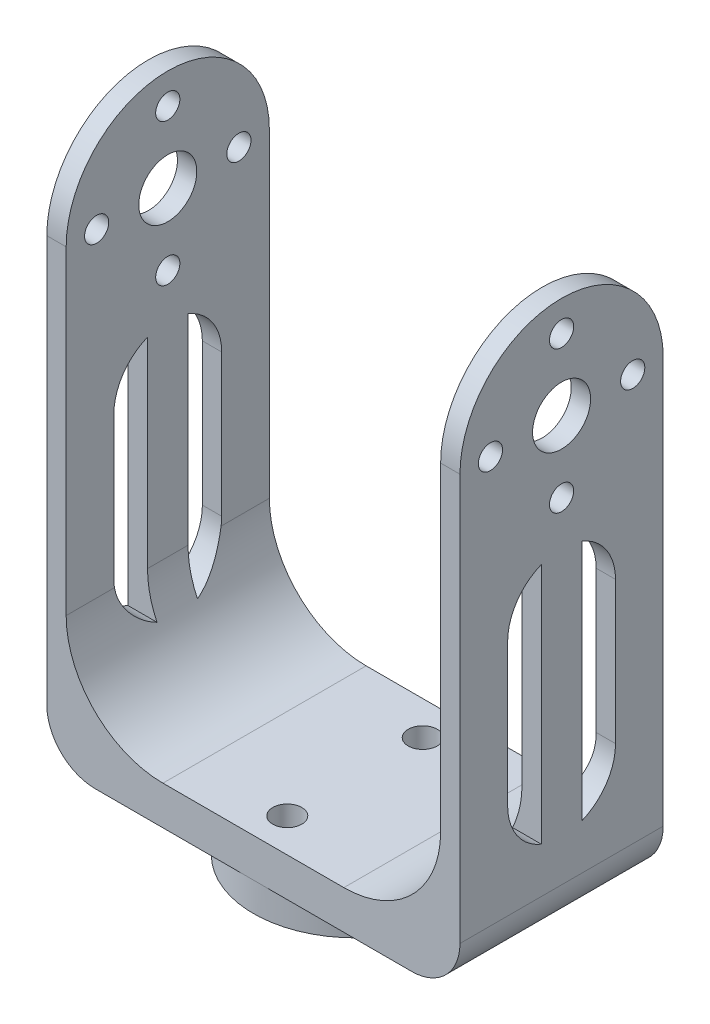
SolidWorks part; units mm, degrees
ref_plane "前视基准面" through (0, 0, 0) normal (0, 0, 1) x (1, 0, 0)
ref_plane "上视基准面" through (0, 0, 0) normal (0, 1, 0) x (1, 0, 0)
ref_plane "右视基准面" through (0, 0, 0) normal (1, 0, 0) x (0, 0, -1)
other "Configuration Table"
sketch "草图1" plane through (0, 0, 0) normal (0, 1, 0) x (1, 0, 0)
  line L0 (0, 10.5) -> (0, -10.5) construction
  line L1 (-21.35, 10.5) -> (21.35, 10.5)
  line L2 (-21.35, 10.5) -> (-21.35, -10.5)
  line L3 (-21.35, -10.5) -> (21.35, -10.5)
  line L4 (21.35, 10.5) -> (21.35, -10.5)
  line L5 (-21.35, 10.5) -> (21.35, -10.5) construction
  line L6 (-21.35, -10.5) -> (21.35, 10.5) construction
  line L7 (-21.35, 0) -> (21.35, 0) construction
  line L8 (8.018, 1.5509) -> (12.9126, 1.5509)
  line L9 (8.018, -1.5509) -> (12.9126, -1.5509)
  line L10 (-8.018, -1.5509) -> (-12.9126, -1.5509)
  line L11 (-8.018, 1.5509) -> (-12.9126, 1.5509)
  circle A0 centre (7.5, 5) radius 1.5
  arc A1 (12.9126, 1.5509) -> (14.6975, 0) centre (13.0296, -0.117) cw
  arc A2 (12.9126, -1.5509) -> (14.6975, 0) centre (13.0296, 0.117) ccw
  circle A3 centre (7.5, -5) radius 1.5
  circle A4 centre (-7.5, -5) radius 1.5
  arc A5 (-12.9126, -1.5509) -> (-14.6975, 0) centre (-13.0296, 0.117) cw
  arc A6 (-12.9126, 1.5509) -> (-14.6975, 0) centre (-13.0296, -0.117) ccw
  circle A7 centre (-7.5, 5) radius 1.5
  spline S0 degree 3 poles (0, 7.4073) (2.0925, 7.358) (3.0437, 2.9519) (6.0077, 1.6267) (8.018, 1.5509) knots 0 0 0 0 0.496823 1 1 1 1
  spline S1 degree 3 poles (0, -7.4073) (2.0925, -7.358) (3.0437, -2.9519) (6.0077, -1.6267) (8.018, -1.5509) knots 0 0 0 0 0.496823 1 1 1 1
  spline S2 degree 3 poles (0, -7.4073) (-2.0925, -7.358) (-3.0437, -2.9519) (-6.0077, -1.6267) (-8.018, -1.5509) knots 0 0 0 0 0.496823 1 1 1 1
  spline S3 degree 3 poles (0, 7.4073) (-2.0925, 7.358) (-3.0437, 2.9519) (-6.0077, 1.6267) (-8.018, 1.5509) knots 0 0 0 0 0.496823 1 1 1 1
  point P0 (0, 0)
  point P6 (7.5, 5)
  point P13 (0, 7.4073)
  point P14 (2.4183, 5.7294)
  point P15 (3.5345, 3.7404)
  point P16 (4.8936, 2.4067)
  point P17 (8.018, 1.5509)
  dimension "D5" = 3
  dimension "D1" = 21
  dimension "D2" = 42.7
  dimension "D3" = 7.5
  dimension "D4" = 5
extrude "凸台-拉伸1" add sketch "草图1" along normal blind 2
sketch "草图2" plane through (-21.35, 0, 0) normal (-1, 0, 0) x (0, 0, 1)
  line L0 (-10.5, 2) -> (-10.5, 46)
  line L1 (10.5, 2) -> (10.5, 46)
  line L2 (-10.5, 46) -> (10.5, 46) construction
  line L3 (0, 46) -> (0, 56.5) construction
  line L4 (-10.5, 2) -> (10.5, 2)
  line L5 (0, 46) -> (0, 38.65) construction
  line L6 (-2.0914, 33.7195) -> (-2.0914, 8.6826)
  line L7 (0, 28.5519) -> (0, 13.8502) construction
  line L8 (5.5747, 28.5519) -> (5.5747, 13.8502)
  line L9 (-5.5747, 28.5519) -> (-5.5747, 13.8502)
  line L10 (2.0914, 33.7195) -> (2.0914, 8.6826)
  arc A0 (-10.5, 46) -> (10.5, 46) centre (0, 46) cw
  circle A1 centre (0, 38.65) radius 1.25
  circle A2 centre (-7.35, 46) radius 1.25
  circle A3 centre (0, 53.35) radius 1.25
  circle A4 centre (7.35, 46) radius 1.25
  circle A5 centre (0, 46) radius 3
  arc A6 (5.5747, 28.5519) -> (2.0914, 33.7195) centre (0, 28.5519) ccw
  arc A7 (-5.5747, 13.8502) -> (-2.0914, 8.6826) centre (0, 13.8502) ccw
  arc A8 (-2.0914, 33.7195) -> (-5.5747, 28.5519) centre (0, 28.5519) ccw
  arc A9 (2.0914, 8.6826) -> (5.5747, 13.8502) centre (0, 13.8502) ccw
  point P12 (-7.35, 46)
  point P13 (7.35, 46)
  point P14 (0, 53.35)
  point P24 (0, 21.201)
  point P29 (-2.0914, 33.7195)
  dimension "D5" = 2.5
  dimension "D9" = 2.5
  dimension "D10" = 2.5
  dimension "D11" = 2.5
  dimension "D12" = 6
  dimension "D1" = 44
  dimension "D2" = 44
  dimension "D3" = 10.5
  dimension "D4" = 7.35
  dimension "D6" = 7.35
  dimension "D7" = 7.35
  dimension "D8" = 7.35
extrude "凸台-拉伸2" add sketch "草图2" against normal blind 2
mirror "镜向1" about plane through (0, 0, 0) normal (1, 0, 0) of "凸台-拉伸2"
sketch "草图3" plane through (0, 0, 0) normal (0, -1, 0) x (1, 0, 0)
  line L1 (-21.35, 10.5) -> (21.35, 10.5)
  line L2 (-21.35, 10.5) -> (-21.35, -10.5)
  line L3 (-21.35, -10.5) -> (21.35, -10.5)
  line L4 (21.35, 10.5) -> (21.35, -10.5)
extrude "凸台-拉伸3" add sketch "草图3" along normal blind 1 and the other way blind 3
sketch "草图4" plane through (0, -1, 0) normal (0, -1, 0) x (1, 0, 0)
  line L0 (-21.35, 10.5) -> (21.35, -10.5) construction
  line L1 (21.35, 10.5) -> (-21.35, -10.5) construction
  line L2 (0, 0) -> (0, 7) construction
  line L3 (0, 0) -> (0, -7) construction
  circle A0 centre (0, 7) radius 1.5
  circle A1 centre (0, -7) radius 1.5
  circle A2 centre (0, 0) radius 10.5
  dimension "D3" = 3
  dimension "D4" = 3
  dimension "D1" = 7
  dimension "D2" = 7
extrude "凸台-拉伸4" add sketch "草图4" along normal blind 3
fillet "圆角1" radius 10 2 edges at (19.35, 3, 0) (-19.35, 3, 0)
fillet "圆角2" radius 5 2 edges at (21.35, -1, 0) (-21.35, -1, 0)
sketch "草图6" plane through (0, -1, 0) normal (0, -1, 0) x (1, 0, 0)
  circle A0 centre (0, 7) radius 1.5
  circle A1 centre (0, -7) radius 1.5
extrude "切除-拉伸1" cut sketch "草图6" against normal up to surface (4 mm away) up to face at (0, 3, 0)
